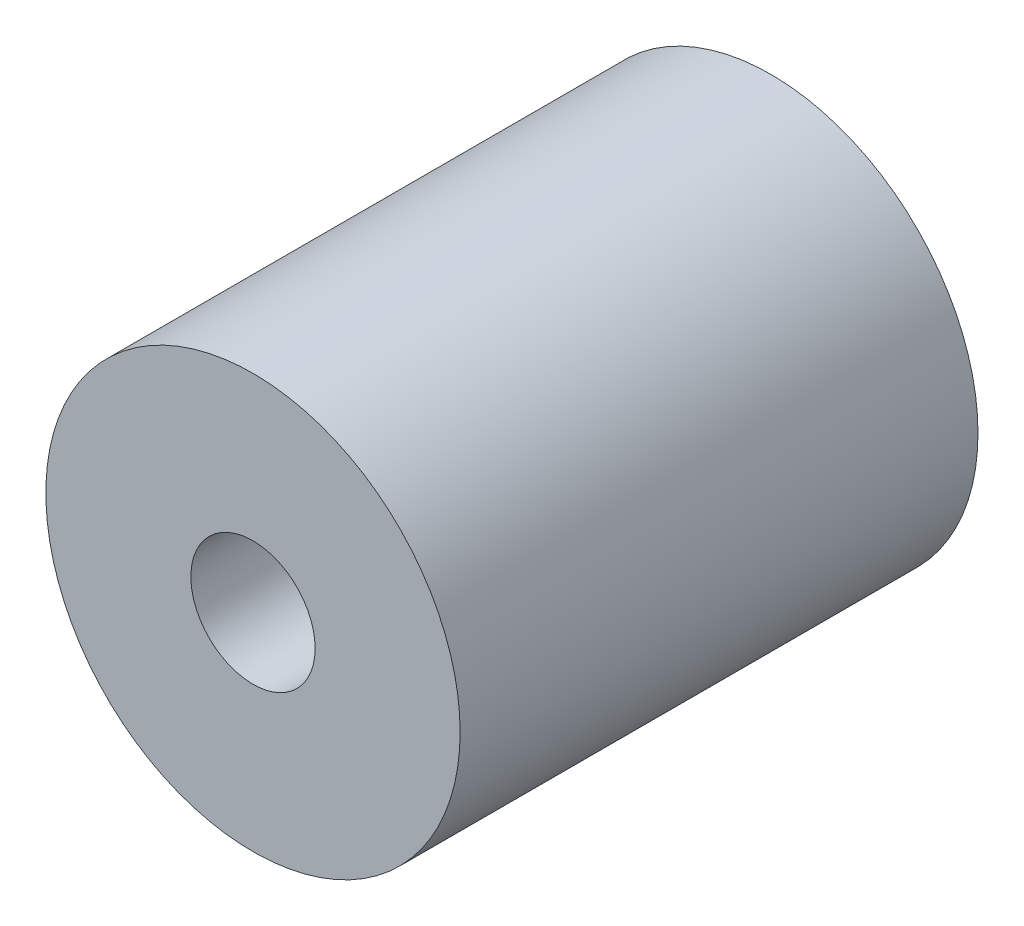
SolidWorks part; units mm, degrees
material "Chrome Stainless Steel"
ref_plane "Front Plane" through (0, 0, 0) normal (0, 0, 1) x (1, 0, 0)
ref_plane "Top Plane" through (0, 0, 0) normal (0, 1, 0) x (1, 0, 0)
ref_plane "Right Plane" through (0, 0, 0) normal (1, 0, 0) x (0, 0, -1)
sketch "Sketch1" plane through (0, 0, 0) normal (0, 0, 1) x (1, 0, 0)
  circle A0 centre (0, 0) radius 3
  circle A1 centre (0, 0) radius 10
  dimension "D1" = 6
  dimension "D2" = 20
extrude "Boss-Extrude1" add sketch "Sketch1" along normal blind 7.5 and the other way blind 7.5 contours A1 A0 | A0 region at (0, 0, 0) region at (-9.7172, 0, 0)
extrude "Boss-Extrude2" add sketch "Sketch1<2>" along normal blind 12.5 and the other way blind 12.5
sketch "Sketch1<2>" plane through (0, 0, 0) normal (0, 0, 1) x (1, 0, 0) same geometry as "Sketch1"
